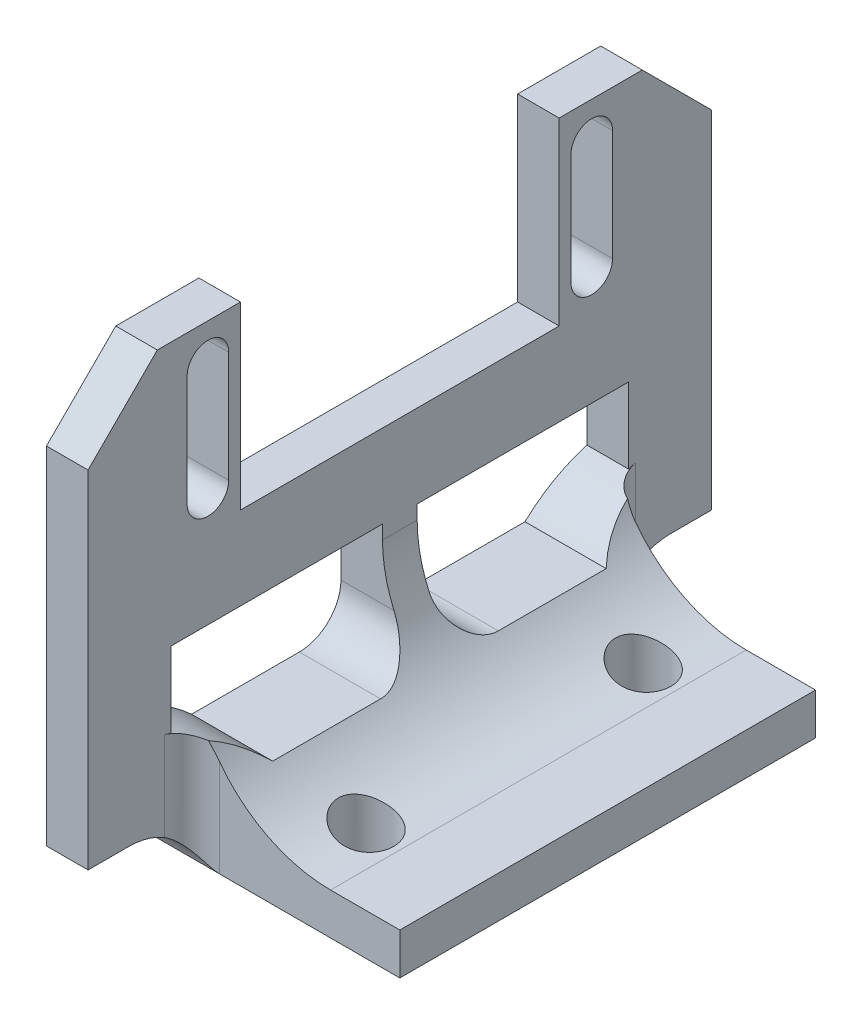
SolidWorks part; units mm, degrees
ref_plane "Front Plane" through (0, 0, 0) normal (0, 0, 1) x (1, 0, 0)
ref_plane "Top Plane" through (0, 0, 0) normal (0, 1, 0) x (1, 0, 0)
ref_plane "Right Plane" through (0, 0, 0) normal (1, 0, 0) x (0, 0, -1)
sketch "Sketch1" plane through (0, 0, 0) normal (0, 0, 1) x (1, 0, 0)
  line L0 (-3, -3) -> (-3, 15)
  line L1 (0, 0) -> (15, 0)
  line L2 (0, 0) -> (0, 15)
  line L5 (-3, -3) -> (15, -3)
  line L6 (0, 15) -> (-3, 15)
  line L7 (15, 0) -> (15, -3)
  dimension "D1" = 15
  dimension "D2" = 15
  dimension "D3" = 3
extrude "Boss-Extrude1" add sketch "Sketch1" along normal blind 30
sketch "Sketch2" plane through (0, 0, 0) normal (1, 0, 0) x (0, 0, -1)
  line L0 (-30, 0) -> (-37.5, 0)
  line L2 (-37.5, 15) -> (-37.5, 30)
  line L3 (-37.5, 30) -> (7.5, 30)
  line L12 (7.5, 15) -> (7.5, 30)
  line L13 (-30, 0) -> (0, 0) construction
  line L14 (-37.5, 0) -> (-37.5, 15)
  line L15 (0, 0) -> (7.5, 0)
  line L16 (7.5, 0) -> (7.5, 15)
  dimension "D2" = 45
  dimension "D3" = 15
extrude "Boss-Extrude2" add sketch "Sketch2" against normal blind 3
sketch "Sketch3" plane through (-3, 0, 0) normal (-1, 0, 0) x (0, 0, 1)
  line L0 (37.5, 30) -> (-7.5, 30) construction
  line L1 (3.5, 30) -> (26.5, 30)
  line L2 (3.5, 30) -> (3.5, 17)
  line L3 (3.5, 17) -> (26.5, 17)
  line L4 (26.5, 30) -> (26.5, 17)
  line L5 (30, -3) -> (0, -3) construction
  point P6 (15, 17)
  point P9 (15, -3)
  dimension "D1" = 23
  dimension "D2" = 13
extrude "Cut-Extrude1" cut sketch "Sketch3" against normal blind 3
sketch "Sketch4" plane through (-3, 0, 0) normal (-1, 0, 0) x (0, 0, 1)
  line L0 (30.35, 19.2854) -> (30.35, 27.2854)
  line L3 (27.35, 27.2854) -> (27.35, 19.2854)
  line L9 (15, -3) -> (15, 30) construction
  line L10 (30, -3) -> (0, -3) construction
  line L11 (2.65, 27.2854) -> (2.65, 19.2854)
  line L12 (-0.35, 19.2854) -> (-0.35, 27.2854)
  line L13 (26.5, 17) -> (26.5, 30) construction
  line L15 (37.5, 30) -> (26.5, 30) construction
  arc A2 (27.35, 19.2854) -> (30.35, 19.2854) centre (28.85, 19.2854) ccw
  arc A4 (30.35, 27.2854) -> (27.35, 27.2854) centre (28.85, 27.2854) ccw
  arc A5 (-0.35, 27.2854) -> (2.65, 27.2854) centre (1.15, 27.2854) cw
  arc A6 (2.65, 19.2854) -> (-0.35, 19.2854) centre (1.15, 19.2854) cw
  point P14 (0, 0)
  point P21 (28.4691, 30)
  dimension "D4" = 1.5
  dimension "D1" = 8
  dimension "D2" = 2.35
  dimension "D3" = 2.7146
extrude "Cut-Extrude3" cut sketch "Sketch4" against normal blind 10
fillet "Fillet1" radius 10 1 edges at (0, 0, 15)
fillet "Fillet2" radius 5 2 edges at (-1.5, 0, 30) (-1.5, 0, 0)
chamfer "Chamfer1" distance 5 angle 45 2 edges at (-1.5, 30, 37.5) (-1.5, 30, -7.5)
sketch "Sketch5" plane through (0, -3, 0) normal (0, -1, 0) x (1, 0, 0)
  line L0 (7.5636, 5) -> (7.5636, 25) construction
  line L1 (15, 30) -> (15, 0) construction
  circle A0 centre (7.5636, 5) radius 2
  circle A1 centre (7.5636, 25) radius 2
  point P4 (7.5636, 15)
  point P7 (15, 15)
  dimension "D1" = 4
  dimension "D2" = 20
extrude "Cut-Extrude4" cut sketch "Sketch5" against normal through all
sketch "Sketch6" plane through (-3, 0, 0) normal (-1, 0, 0) x (0, 0, 1)
  line L0 (31.5, 5.5592) -> (31.5, 11)
  line L1 (31.5, 11) -> (31.5, 11)
  line L2 (31.5, 11) -> (31.5, 11)
  line L3 (31.5, 11) -> (31.5, 11)
  line L4 (31.5, 11) -> (-1.5, 11)
  line L5 (-1.5, 11) -> (-1.5, 11)
  line L6 (-1.5, 11) -> (-1.5, 11)
  line L7 (-1.5, 11) -> (-1.5, 11)
  line L8 (-1.5, 11) -> (-1.5, 5.5592)
  line L9 (-1.5, 5.5592) -> (-1.5, 5.5592)
  line L10 (2.9673, 3) -> (27.0327, 3)
  line L11 (31.5, 5.5592) -> (31.5, 5.5592)
  line L12 (37.5, 0) -> (37.5, 25)
  line L13 (37.5, 25) -> (32.5, 30)
  line L14 (32.5, 30) -> (26.5, 30)
  line L15 (26.5, 30) -> (26.5, 17)
  line L16 (26.5, 17) -> (3.5, 17)
  line L17 (3.5, 17) -> (3.5, 30)
  line L18 (3.5, 30) -> (-2.5, 30)
  line L19 (-2.5, 30) -> (-7.5, 25)
  line L20 (-7.5, 25) -> (-7.5, 0)
  line L21 (-7.5, 0) -> (-4.5826, 0)
  line L22 (0, -3) -> (30, -3)
  line L23 (34.5826, 0) -> (37.5, 0)
  line L24 (37.5, 0) -> (37.5, 25)
  line L25 (37.5, 25) -> (32.5, 30)
  line L26 (32.5, 30) -> (26.5, 30)
  line L27 (26.5, 30) -> (26.5, 17)
  line L28 (26.5, 17) -> (3.5, 17)
  line L29 (3.5, 17) -> (3.5, 30)
  line L30 (3.5, 30) -> (-2.5, 30)
  line L31 (-2.5, 30) -> (-7.5, 25)
  line L32 (-7.5, 25) -> (-7.5, 0)
  line L33 (-7.5, 0) -> (-4.5826, 0)
  line L34 (0, -3) -> (30, -3)
  line L35 (34.5826, 0) -> (37.5, 0)
  line L36 (15, 11) -> (15, 3) construction
  line L37 (13.7491, 3) -> (13.7491, 11)
  line L38 (16.2509, 3) -> (16.2509, 11)
  arc A0 (2.9673, 3) -> (-1.5, 5.5592) centre (-4.5826, -5) ccw
  arc A1 (31.5, 5.5592) -> (27.0327, 3) centre (34.5826, -5) ccw
  arc A2 (0, -3) -> (-4.5826, 0) centre (-4.5826, -5) ccw
  arc A3 (34.5826, 0) -> (30, -3) centre (34.5826, -5) ccw
  arc A4 (0, -3) -> (-4.5826, 0) centre (-4.5826, -5) ccw
  arc A5 (34.5826, 0) -> (30, -3) centre (34.5826, -5) ccw
  dimension "D1" = 0
  dimension "D2" = 6
extrude "Cut-Extrude5" cut sketch "Sketch6" against normal through all contours A0 L10 L37 L4 L8 | A1 L0 L4 L38 L10
fillet "Fillet3" radius 3 2 edges at (-0.0707, 3, 16.2509) (-0.0707, 3, 13.7491)
fillet "Fillet4" radius 2 2 edges at (0, 1, 0) (0, 1, 30)
